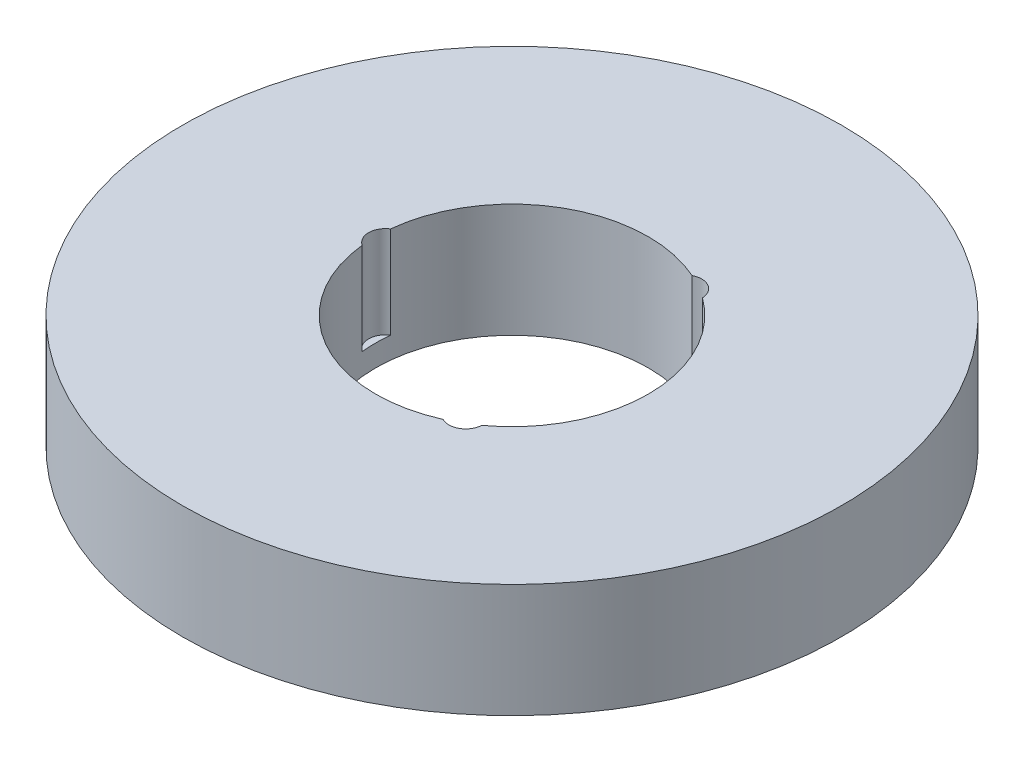
SolidWorks part; units mm, degrees
ref_plane "Front Plane" through (0, 0, 0) normal (0, 0, 1) x (1, 0, 0)
ref_plane "Top Plane" through (0, 0, 0) normal (0, 1, 0) x (1, 0, 0)
ref_plane "Right Plane" through (0, 0, 0) normal (1, 0, 0) x (0, 0, -1)
sketch "Sketch1" plane through (0, 0, 0) normal (0, 1, 0) x (1, 0, 0)
  circle A0 centre (0, 0) radius 72.5
  dimension "FLANGE_OD" = 145
extrude "Boss-Extrude1" add sketch "Sketch1" along normal blind 25
sketch "Sketch2" plane through (0, 0, 0) normal (0, 1, 0) x (1, 0, 0)
  circle A0 centre (0, 0) radius 30
  dimension "BORE_D" = 60
extrude "Cut-Extrude1" cut sketch "Sketch2" along normal through all
sketch "Sketch3" plane through (0, 25, 0) normal (0, 1, 0) x (1, 0, 0)
  circle A0 centre (0, 0) radius 27.8426 construction
  circle A1 centre (-27.8426, 0) radius 3.6985
  dimension "BOLT_D" = 7.397
  dimension "BOLT_PCD" = 55.6853
extrude "Cut-Extrude2" cut sketch "Sketch3" against normal blind 20.248
pattern_circular "CirPattern1" count 3 over 360 about axis through (0, 0, 0) along (0, 1, 0) of "Cut-Extrude2"
